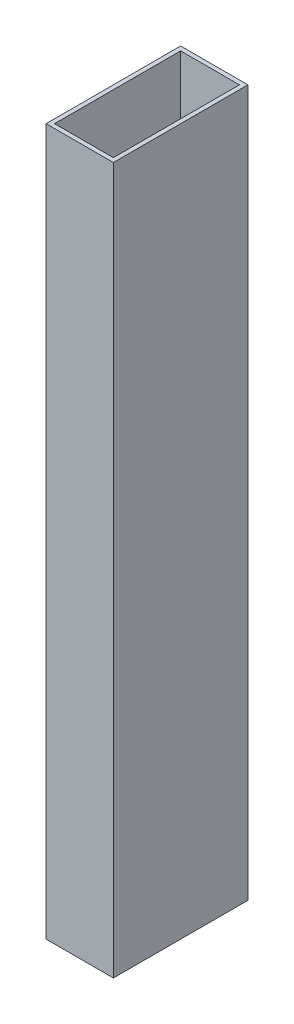
SolidWorks part; units mm, degrees
material "6061-T6 (SS)"
ref_plane "Front" through (0, 0, 0) normal (0, 0, 1) x (1, 0, 0)
ref_plane "Top" through (0, 0, 0) normal (0, 1, 0) x (1, 0, 0)
ref_plane "Right" through (0, 0, 0) normal (1, 0, 0) x (0, 0, -1)
sketch "Sketch1" plane through (0, 0, 0) normal (0, 1, 0) x (1, 0, 0)
  line L1 (12.7, 25.4) -> (-12.7, 25.4)
  line L2 (12.7, 25.4) -> (12.7, -25.4)
  line L3 (12.7, -25.4) -> (-12.7, -25.4)
  line L4 (-12.7, 25.4) -> (-12.7, -25.4)
  line L5 (12.7, 25.4) -> (-12.7, -25.4) construction
  line L6 (12.7, -25.4) -> (-12.7, 25.4) construction
  point P0 (0, 0)
  dimension "D1" = 25.4
  dimension "D2" = 50.8
extrude "Extrude-Thin1" add sketch "Sketch1" along normal up to surface (266.7 mm away) thin thin type one direction reverse wall 1.5875
